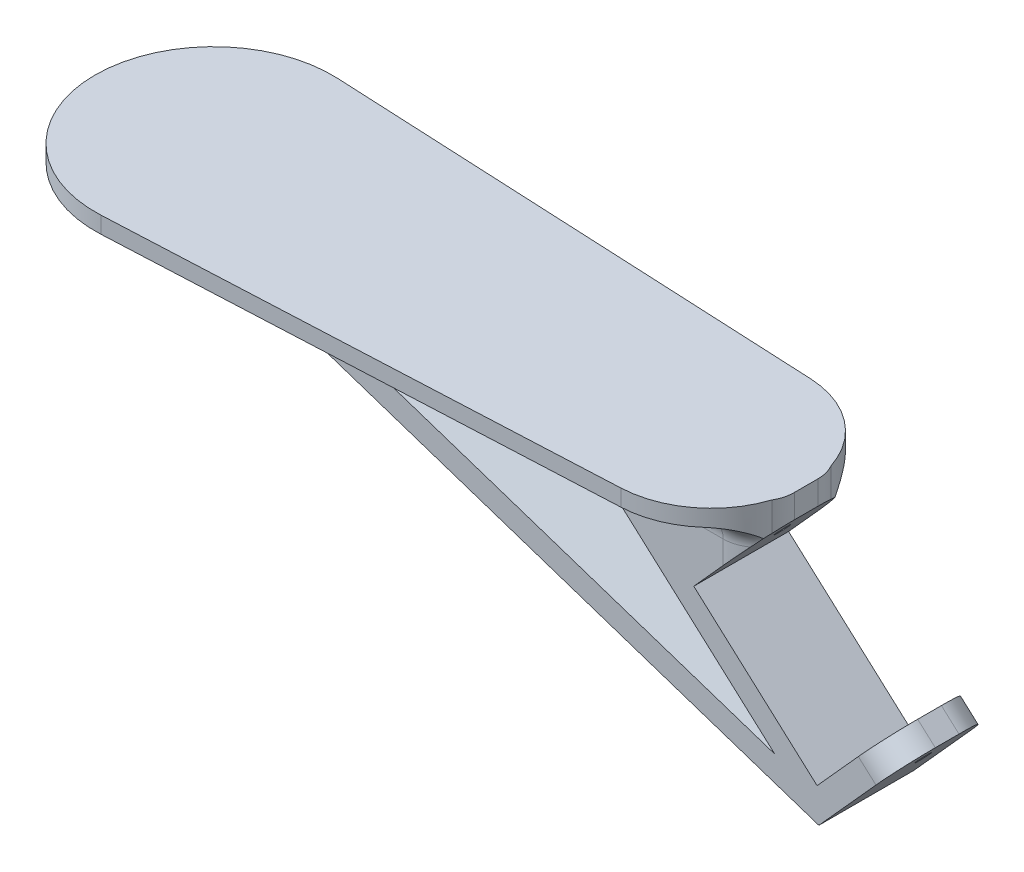
SolidWorks part; units mm, degrees
ref_plane "Plan de face" through (0, 0, 0) normal (0, 0, 1) x (1, 0, 0)
ref_plane "Plan de dessus" through (0, 0, 0) normal (0, 1, 0) x (1, 0, 0)
ref_plane "Plan de droite" through (0, 0, 0) normal (1, 0, 0) x (0, 0, -1)
sketch "Esquisse1" plane through (0, 0, 0) normal (0, 0, 1) x (1, 0, 0)
  line L0 (-59.4516, 53.5304) -> (-86.8859, 23.0615)
  line L1 (-309.4516, 63.5304) -> (-59.4516, 63.5304)
  line L2 (-309.4516, 63.5304) -> (-309.4516, 53.5304)
  line L3 (-309.4516, 53.5304) -> (-59.4516, 53.5304)
  line L4 (-59.4516, 63.5304) -> (-59.4516, 53.5304)
  line L5 (-86.8859, 23.0615) -> (-120.7251, 53.5304)
  line L6 (0, 0) -> (-27.4344, -30.4689)
  line L7 (0, 0) -> (-27.4344, -30.4689)
  line L8 (0, 0) -> (-7.4314, 6.6913)
  line L9 (-27.4344, -30.4689) -> (-34.8658, -23.7776)
  line L10 (-7.4314, 6.6913) -> (-34.8658, -23.7776)
  line L11 (-86.8859, 23.0615) -> (-34.8658, -23.7776)
  line L12 (-27.4344, -30.4689) -> (-34.1257, -37.9004)
  line L13 (-135.6699, 53.5304) -> (-34.1257, -37.9004)
  line L14 (-309.4516, 53.5304) -> (-34.1257, -37.9004)
  line L15 (-277.7216, 53.5304) -> (-52.6662, -21.2064)
  dimension "D1" = 10
  dimension "D2" = 41
  dimension "D3" = 70
  dimension "D4" = 132
  dimension "D5" = 10
  dimension "D6" = 250
  dimension "D7" = 10
  dimension "D8" = 10
extrude "Boss.-Extru.1" add sketch "Esquisse1" along normal blind 40
fillet "Congé2" radius 15 4 edges at (-3.7157, 3.3457, 0) (-3.7157, 3.3457, 40) (-59.4516, 58.5304, 0) (-59.4516, 58.5304, 40)
sketch "Esquisse11" plane through (0, 63.5304, 0) normal (0, 1, 0) x (1, 0, 0)
  line L0 (-59.4516, -20) -> (-309.4516, -20) construction
  line L1 (-59.4516, -25) -> (-59.4516, -15) construction
  line L3 (-307.0706, 29.9433) -> (-97.5468, 19.9546)
  line L4 (-307.0706, -69.9433) -> (-97.5468, -59.9546)
  circle A0 centre (-309.4516, -20) radius 50
  circle A1 centre (-99.4516, -20) radius 40
  dimension "D1" = 100
  dimension "D2" = 80
  dimension "D3" = 250
extrude "Boss.-Extru.5" add sketch "Esquisse11" against normal blind 7
fillet "Congé6" radius 10 5 edges at (-66.9388, 56.5304, 2.017) (-66.9388, 56.5304, 37.983) (-191.9516, 56.5304, 0) (-191.9516, 56.5304, 40) (-309.4516, 56.5304, 20)
sketch "Sketch1" plane through (0, 0, 0) normal (0.7431, -0.6691, 0) x (0, 0, -1)
  line L0 (-20, -51) -> (-20, 0) construction
  line L1 (-40, -51) -> (0, -51) construction
  line L2 (-25, 0) -> (-15, 0) construction
  circle A0 centre (-20, -15) radius 3
  point P8 (-20, -15.6126)
  dimension "D1" = 6
  dimension "D2" = 15
extrude "Cut-Extrude1" cut sketch "Sketch1" against normal blind 86
